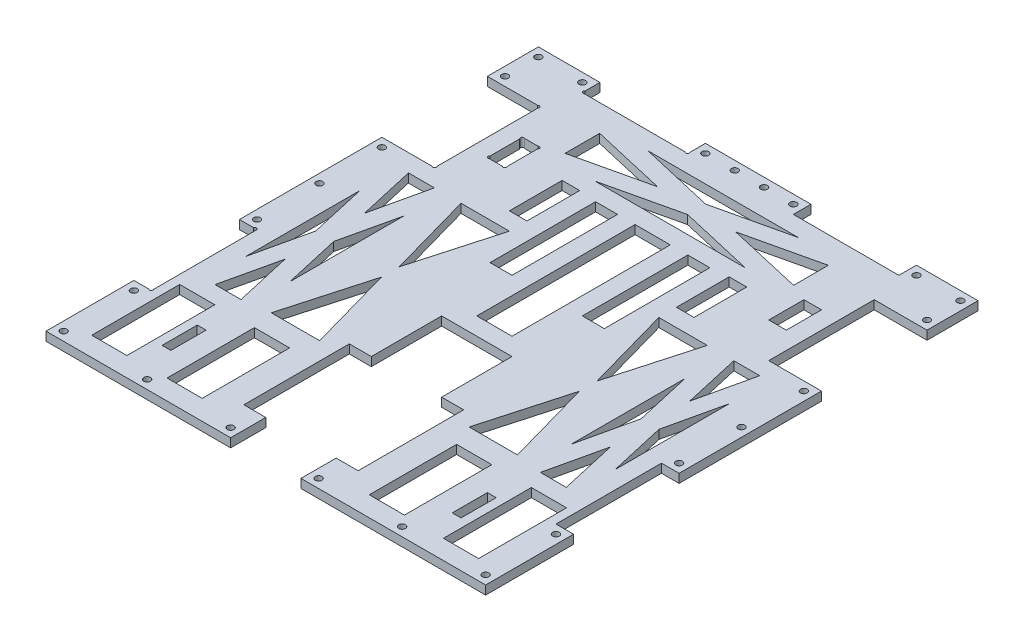
SolidWorks part; units mm, degrees
material "7050-T73510"
ref_plane "Front Plane" through (0, 0, 0) normal (0, 0, 1) x (1, 0, 0)
ref_plane "Top Plane" through (0, 0, 0) normal (0, 1, 0) x (1, 0, 0)
ref_plane "Right Plane" through (0, 0, 0) normal (1, 0, 0) x (0, 0, -1)
sketch "Sketch1" plane through (0, 0, 0) normal (0, 1, 0) x (1, 0, 0)
  line L1 (-158.75, -177.8) -> (158.75, -177.8)
  line L2 (-158.75, -177.8) -> (-158.75, 177.8)
  line L3 (-158.75, 177.8) -> (158.75, 177.8)
  line L4 (158.75, -177.8) -> (158.75, 177.8)
  line L5 (-158.75, -177.8) -> (158.75, 177.8) construction
  line L6 (-158.75, 177.8) -> (158.75, -177.8) construction
  point P0 (0, 0)
  dimension "D1" = 355.6
  dimension "D2" = 317.5
extrude "Boss-Extrude1" add sketch "Sketch1" along normal blind 6.35
sketch "Sketch2" plane through (0, 6.35, 0) normal (0, 1, 0) x (1, 0, 0)
  line L0 (-158.75, -177.8) -> (158.75, -177.8) construction
  line L1 (-25.4, -25.4) -> (25.4, -25.4)
  line L2 (-25.4, -25.4) -> (-25.4, -177.8)
  line L3 (-25.4, -177.8) -> (25.4, -177.8)
  line L4 (25.4, -25.4) -> (25.4, -177.8)
  line L5 (-25.4, -25.4) -> (25.4, -177.8) construction
  line L6 (-25.4, -177.8) -> (25.4, -25.4) construction
  point P0 (0, -101.6)
  dimension "D1" = 152.4
  dimension "D2" = 50.8
extrude "Cut-Extrude1" cut sketch "Sketch2" against normal through all
sketch "Sketch3" plane through (0, 6.35, 0) normal (0, 1, 0) x (1, 0, 0)
  line L0 (158.75, -177.8) -> (158.75, 177.8) construction
  line L5 (146.05, 140.97) -> (120.65, 140.97)
  line L11 (146.05, 140.97) -> (146.05, 64.77)
  line L13 (146.05, 64.77) -> (120.65, 64.77)
  line L15 (120.65, 140.97) -> (120.65, 64.77)
  line L16 (158.75, 177.8) -> (-158.75, 177.8) construction
  line L17 (107.95, 90.17) -> (95.25, 90.17)
  line L18 (107.95, 90.17) -> (107.95, 115.57)
  line L19 (107.95, 115.57) -> (95.25, 115.57)
  line L20 (95.25, 90.17) -> (95.25, 115.57)
  line L21 (0, -3.4925) -> (0, 3.4925) construction
  line L22 (-95.25, 90.17) -> (-95.25, 115.57)
  line L23 (-107.95, 115.57) -> (-95.25, 115.57)
  line L24 (-107.95, 90.17) -> (-107.95, 115.57)
  line L25 (-107.95, 90.17) -> (-95.25, 90.17)
  line L26 (-120.65, 140.97) -> (-120.65, 64.77)
  line L27 (-146.05, 64.77) -> (-120.65, 64.77)
  line L28 (-146.05, 140.97) -> (-146.05, 64.77)
  line L29 (-146.05, 140.97) -> (-120.65, 140.97)
  point P14 (107.95, 102.87)
  point P15 (120.65, 102.87)
  dimension "D1" = 25.4
  dimension "D2" = 12.7
  dimension "D3" = 12.7
  dimension "D4" = 12.7
  dimension "D5" = 25.4
  dimension "D6" = 76.2
  dimension "D7" = 36.83
extrude "Cut-Extrude2" cut sketch "Sketch3" against normal through all contours L5 L15 L13 L11 | L20 L17 L18 L19 | L29 L28 L27 L26 | L24 L25 L22 L23 | L26 L27 L28 L29 region at (133.35, 6.35, -102.87) region at (101.6, 6.35, -102.87) region at (-101.6, 6.35, -102.87) region at (-133.35, 6.35, -102.87)
sketch "Sketch4" plane through (0, 6.35, 0) normal (0, 1, 0) x (1, 0, 0)
  line L0 (-158.75, 177.8) -> (-158.75, -177.8) construction
  line L1 (-158.75, 140.97) -> (-146.05, 140.97)
  line L2 (-158.75, 140.97) -> (-158.75, 64.77)
  line L3 (-158.75, 64.77) -> (-146.05, 64.77)
  line L4 (-146.05, 140.97) -> (-146.05, 64.77)
  line L5 (0, -3.4925) -> (0, 3.4925) construction
  line L6 (-158.75, -114.3) -> (-146.05, -114.3)
  line L7 (-158.75, -114.3) -> (-158.75, -38.1)
  line L8 (-158.75, -38.1) -> (-146.05, -38.1)
  line L9 (-146.05, -114.3) -> (-146.05, -38.1)
  line L10 (158.75, 64.77) -> (146.05, 64.77)
  line L11 (146.05, 140.97) -> (146.05, 64.77)
  line L12 (158.75, 140.97) -> (146.05, 140.97)
  line L13 (158.75, 140.97) -> (158.75, 64.77)
  line L14 (158.75, -38.1) -> (146.05, -38.1)
  line L15 (146.05, -114.3) -> (146.05, -38.1)
  line L16 (158.75, -114.3) -> (146.05, -114.3)
  line L17 (158.75, -114.3) -> (158.75, -38.1)
  line L18 (158.75, 177.8) -> (-158.75, 177.8) construction
  line L19 (114.3, 165.1) -> (38.1, 165.1)
  line L20 (-114.3, 177.8) -> (-38.1, 177.8)
  line L21 (-114.3, 177.8) -> (-114.3, 165.1)
  line L22 (-114.3, 165.1) -> (-38.1, 165.1)
  line L23 (-38.1, 177.8) -> (-38.1, 165.1)
  line L24 (38.1, 177.8) -> (38.1, 165.1)
  line L25 (114.3, 177.8) -> (38.1, 177.8)
  line L26 (114.3, 177.8) -> (114.3, 165.1)
  line L27 (-25.4, -25.4) -> (-25.4, -177.8) construction
  line L28 (-25.4, -152.4) -> (-41.275, -152.4)
  line L29 (-25.4, -152.4) -> (-25.4, -76.2)
  line L30 (-25.4, -76.2) -> (-41.275, -76.2)
  line L31 (-41.275, -152.4) -> (-41.275, -76.2)
  line L32 (-158.75, -177.8) -> (-25.4, -177.8) construction
  line L33 (25.4, 101.6) -> (41.275, 101.6)
  line L34 (-25.4, 25.4) -> (-41.275, 25.4)
  line L35 (-25.4, 25.4) -> (-25.4, 101.6)
  line L36 (-25.4, 101.6) -> (-41.275, 101.6)
  line L37 (-41.275, 25.4) -> (-41.275, 101.6)
  line L38 (41.275, 25.4) -> (41.275, 101.6)
  line L39 (25.4, 25.4) -> (41.275, 25.4)
  line L40 (25.4, 25.4) -> (25.4, 101.6)
  line L41 (25.4, -76.2) -> (41.275, -76.2)
  line L42 (41.275, -152.4) -> (41.275, -76.2)
  line L43 (25.4, -152.4) -> (41.275, -152.4)
  line L44 (25.4, -152.4) -> (25.4, -76.2)
  dimension "D1" = 12.7
  dimension "D2" = 12.7
  dimension "D3" = 76.2
  dimension "D4" = 76.2
  dimension "D5" = 36.83
  dimension "D6" = 215.9
  dimension "D7" = 12.7
  dimension "D8" = 76.2
  dimension "D9" = 76.2
  dimension "D10" = 15.875
  dimension "D11" = 76.2
  dimension "D12" = 25.4
  dimension "D13" = 76.2
  dimension "D14" = 15.875
  dimension "D15" = 203.2
  dimension "D16" = 50.8
extrude "Cut-Extrude3" cut sketch "Sketch4" against normal through all
sketch "Sketch5" plane through (0, 6.35, 0) normal (0, 1, 0) x (1, 0, 0)
  line L0 (-41.275, -76.2) -> (-41.275, -152.4) construction
  line L5 (-41.275, 101.6) -> (-41.275, 25.4) construction
  line L6 (-85.725, -100.33) -> (-60.325, -100.33)
  line L7 (-133.35, -87.63) -> (-101.6, -87.63)
  line L8 (-133.35, -87.63) -> (-133.35, 52.07)
  line L9 (-133.35, 52.07) -> (-101.6, 52.07)
  line L10 (-101.6, -87.63) -> (-101.6, 52.07)
  line L11 (-133.35, -87.63) -> (-101.6, 52.07) construction
  line L12 (-133.35, 52.07) -> (-101.6, -87.63) construction
  line L13 (-82.55, 114.3) -> (82.55, 114.3)
  line L14 (-82.55, 114.3) -> (-82.55, 152.4)
  line L15 (-82.55, 152.4) -> (82.55, 152.4)
  line L16 (82.55, 114.3) -> (82.55, 152.4)
  line L17 (-82.55, 114.3) -> (82.55, 152.4) construction
  line L18 (-82.55, 152.4) -> (82.55, 114.3) construction
  line L23 (0, -3.4925) -> (0, 3.4925) construction
  line L24 (-12.7, -12.7) -> (12.7, -12.7)
  line L25 (-146.05, -114.3) -> (-146.05, -38.1) construction
  line L26 (-53.975, 102.87) -> (-66.675, 102.87)
  line L27 (-53.975, 102.87) -> (-53.975, 64.77)
  line L28 (-158.75, 64.77) -> (-158.75, -38.1) construction
  line L29 (-158.75, 64.77) -> (-120.65, 64.77) construction
  line L30 (-85.725, -100.33) -> (-85.725, -163.4194)
  line L31 (-12.7, -12.7) -> (-12.7, 101.6)
  line L32 (-12.7, 101.6) -> (12.7, 101.6)
  line L33 (12.7, -12.7) -> (12.7, 101.6)
  line L34 (-53.975, 64.77) -> (-66.675, 64.77)
  line L35 (-66.675, 102.87) -> (-66.675, 64.77)
  line L36 (53.975, 64.77) -> (66.675, 64.77)
  line L37 (-25.4, 25.4) -> (-25.4, 101.6) construction
  line L38 (-25.4, 101.6) -> (-41.275, 101.6) construction
  line L39 (-95.25, 90.17) -> (-95.25, 115.57) construction
  line L40 (-114.3, 165.1) -> (-38.1, 165.1) construction
  line L41 (-85.725, -163.4194) -> (-60.325, -163.4194)
  line L42 (-60.325, -100.33) -> (-60.325, -163.4194)
  line L43 (-139.5421, 50.6627) -> (-107.7921, -89.0373)
  line L44 (-127.1579, -89.0373) -> (-95.4079, 50.6627)
  line L45 (66.675, 102.87) -> (66.675, 64.77)
  line L46 (53.975, 102.87) -> (66.675, 102.87)
  line L47 (-83.9779, 146.2126) -> (81.1221, 108.1126)
  line L48 (-81.1221, 108.1126) -> (83.9779, 146.2126)
  line L49 (53.975, 102.87) -> (53.975, 64.77)
  line L50 (-88.9, -16.4414) -> (-53.975, -16.4414) construction
  line L51 (-127.1579, 53.4773) -> (-95.4079, -86.2227)
  line L52 (-139.5421, -86.2227) -> (-107.7921, 53.4773)
  line L53 (-88.9, 52.07) -> (-53.975, 52.07) construction
  line L54 (-88.9, 52.07) -> (-88.9, -84.9527) construction
  line L55 (-81.1221, 158.5874) -> (83.9779, 120.4874)
  line L56 (-83.9779, 120.4874) -> (81.1221, 158.5874)
  line L57 (-139.7, -100.33) -> (-114.3, -100.33)
  line L58 (-139.7, -100.33) -> (-139.7, -163.83)
  line L59 (-139.7, -163.83) -> (-114.3, -163.83)
  line L60 (-114.3, -100.33) -> (-114.3, -163.83)
  line L61 (-88.9, -84.9527) -> (-53.975, -84.9527)
  line L62 (-53.975, 52.07) -> (-53.975, -84.9527) construction
  line L63 (-107.95, -144.78) -> (-101.6, -144.78)
  line L64 (-107.95, -144.78) -> (-107.95, -119.38)
  line L65 (-107.95, -119.38) -> (-101.6, -119.38)
  line L66 (-101.6, -144.78) -> (-101.6, -119.38)
  line L67 (-107.95, -144.78) -> (-101.6, -119.38) construction
  line L68 (-107.95, -119.38) -> (-101.6, -144.78) construction
  line L69 (-88.9, -84.9527) -> (-71.4375, -22.7914)
  line L70 (-71.4375, -22.7914) -> (-53.975, -84.9527)
  line L71 (-88.9, 52.07) -> (-53.975, 52.07)
  line L72 (-88.9, 52.07) -> (-71.4375, -10.0914)
  line L73 (-71.4375, -10.0914) -> (-53.975, 52.07)
  point P5 (-117.475, -17.78)
  point P10 (0, 133.35)
  point P15 (0, 44.45)
  point P34 (-104.775, -132.08)
  point P45 (-33.3375, 101.6)
  point P65 (-53.975, -86.2227)
  point P87 (-114.3, -132.08)
  dimension "D3" = 12.7
  dimension "D4" = 19.05
  dimension "D5" = 139.7
  dimension "D6" = 25.4
  dimension "D7" = 12.7
  dimension "D8" = 31.75
  dimension "D9" = 25.4
  dimension "D10" = 12.7
  dimension "D11" = 165.1
  dimension "D12" = 12.7
  dimension "D13" = 12.7
  dimension "D14" = 12.7
  dimension "D17" = 25.4
  dimension "D18" = 63.5
  dimension "D19" = 12.7
  dimension "D20" = 6.35
  dimension "D21" = 38.1
  dimension "D22" = 38.1
  dimension "D23" = 25.4
  dimension "D15" = 114.3
  dimension "D16" = 12.7
  dimension "D24" = 12.7
  dimension "D25" = 12.7
  dimension "D26" = 12.7
  dimension "D27" = 15.3773
  dimension "D28" = 12.7
  dimension "D29" = 6.35
  dimension "D30" = 12.7
extrude "Cut-Extrude4" cut sketch "Sketch5" against normal through all contours L44 L7 L43 | L8 L52 L43 | L51 L52 L9 | L44 L51 L10 | L33 | L32 | L31 | L24 | L48 L13 L47 | L48 L55 L16 | L55 L56 L15 | L14 L56 L47 | L60 L57 L58 L59 | L63 L66 L65 L64 | L42 L6 L30 L41 | L26 L35 L34 L27 | L46 L49 L36 L45 | L61 L70 L69 | L71 L73 L72 region at (-73.025, 6.35, 131.8747) region at (-117.475, 6.35, 73.8975) region at (-130.229, 6.35, 17.78) region at (-104.721, 6.35, 17.78) region at (-117.475, 6.35, -38.3375) region at (0, 6.35, -118.4777) region at (-64.4466, 6.35, -133.35) region at (64.4466, 6.35, -133.35) region at (0, 6.35, -148.2223) region at (0, 6.35, -44.45) region at (-60.325, 6.35, -83.82) region at (60.325, 6.35, -83.82) region at (-127, 6.35, 132.08) region at (-104.775, 6.35, 132.08)
mirror "Mirror1" about plane through (0, 0, 0) normal (1, 0, 0) of "Cut-Extrude4"
sketch "Sketch7" plane through (0, 6.35, 0) normal (0, 1, 0) x (1, 0, 0)
  line L0 (-158.75, -177.8) -> (-25.4, -177.8) construction
  line L1 (-158.75, -114.3) -> (-158.75, -177.8) construction
  line L2 (0, -3.4925) -> (0, 3.4925) construction
  line L3 (-158.75, 177.8) -> (-158.75, 140.97) construction
  line L4 (-114.3, 177.8) -> (-158.75, 177.8) construction
  line L6 (38.1, 177.8) -> (-38.1, 177.8) construction
  line L7 (-38.1, 165.1) -> (-38.1, 177.8) construction
  line L8 (-25.4, -152.4) -> (-25.4, -177.8) construction
  line L9 (-158.75, -114.3) -> (-146.05, -114.3) construction
  line L10 (-158.75, 64.77) -> (-158.75, -38.1) construction
  line L11 (-146.05, -38.1) -> (-158.75, -38.1) construction
  line L12 (-158.75, 64.77) -> (-120.65, 64.77) construction
  circle A0 centre (-152.4, -171.45) radius 2.413
  circle A14 centre (-152.4, 171.45) radius 2.413
  circle A15 centre (-120.65, 171.45) radius 2.413
  circle A16 centre (-152.4, 147.32) radius 2.413
  circle A34 centre (-31.75, 171.45) radius 2.413
  circle A35 centre (-10.5833, 171.45) radius 2.413
  circle A36 centre (10.5833, 171.45) radius 2.413
  circle A37 centre (31.75, 171.45) radius 2.413
  circle A38 centre (-31.75, -171.45) radius 2.413
  circle A39 centre (-92.075, -171.45) radius 2.413
  circle A40 centre (-152.4, -120.65) radius 2.413
  circle A41 centre (-152.4, -31.75) radius 2.413
  circle A42 centre (-152.4, 58.42) radius 2.413
  circle A43 centre (-152.4, 13.335) radius 2.413
  circle A44 centre (31.75, -171.45) radius 2.413
  circle A45 centre (152.4, 13.335) radius 2.413
  circle A46 centre (152.4, 58.42) radius 2.413
  circle A47 centre (152.4, -31.75) radius 2.413
  circle A48 centre (152.4, -120.65) radius 2.413
  circle A49 centre (92.075, -171.45) radius 2.413
  circle A50 centre (152.4, 147.32) radius 2.413
  circle A51 centre (120.65, 171.45) radius 2.413
  circle A52 centre (152.4, 171.45) radius 2.413
  circle A53 centre (152.4, -171.45) radius 2.413
  dimension "D1" = 4.826
  dimension "D6" = 6.35
  dimension "D9" = 4.826
  dimension "D14" = 4.826
  dimension "D4" = 4.826
  dimension "D5" = 4.826
  dimension "D8" = 4.826
  dimension "D20" = 4.826
  dimension "D24" = 4.826
  dimension "D25" = 4.826
  dimension "D2" = 6.35
  dimension "D3" = 6.35
  dimension "D7" = 60.325
  dimension "D10" = 6.35
  dimension "D11" = 6.35
  dimension "D15" = 6.35
  dimension "D16" = 6.35
  dimension "D18" = 6.35
  dimension "D19" = 6.35
  dimension "D21" = 6.35
  dimension "D22" = 6.35
  dimension "D23" = 6.35
  dimension "D26" = 45.085
  dimension "D12" = 2
  dimension "D13" = 2
  dimension "D17" = 4
extrude "Cut-Extrude6" cut sketch "Sketch7" against normal through all
sketch "Sketch8" plane through (0, 6.35, 0) normal (0, 1, 0) x (1, 0, 0)
  circle A0 centre (-39.0994, 165.8837) radius 1.27
  circle A1 centre (-113.5398, 166.1174) radius 1.27
  circle A2 centre (-121.56, 140.0841) radius 1.27
  circle A3 centre (-121.5656, 65.6501) radius 1.27
  circle A4 centre (-147.253, -38.507) radius 1.27
  circle A5 centre (-147.0444, -113.51) radius 1.27
  circle A6 centre (-107.1943, 114.5493) radius 1.27
  circle A7 centre (-96.0341, 114.5709) radius 1.27
  circle A8 centre (-107.1845, 91.1833) radius 1.27
  circle A10 centre (-96.2084, 91.0033) radius 1.27
extrude "Cut-Extrude7" cut sketch "Sketch8" against normal through all
